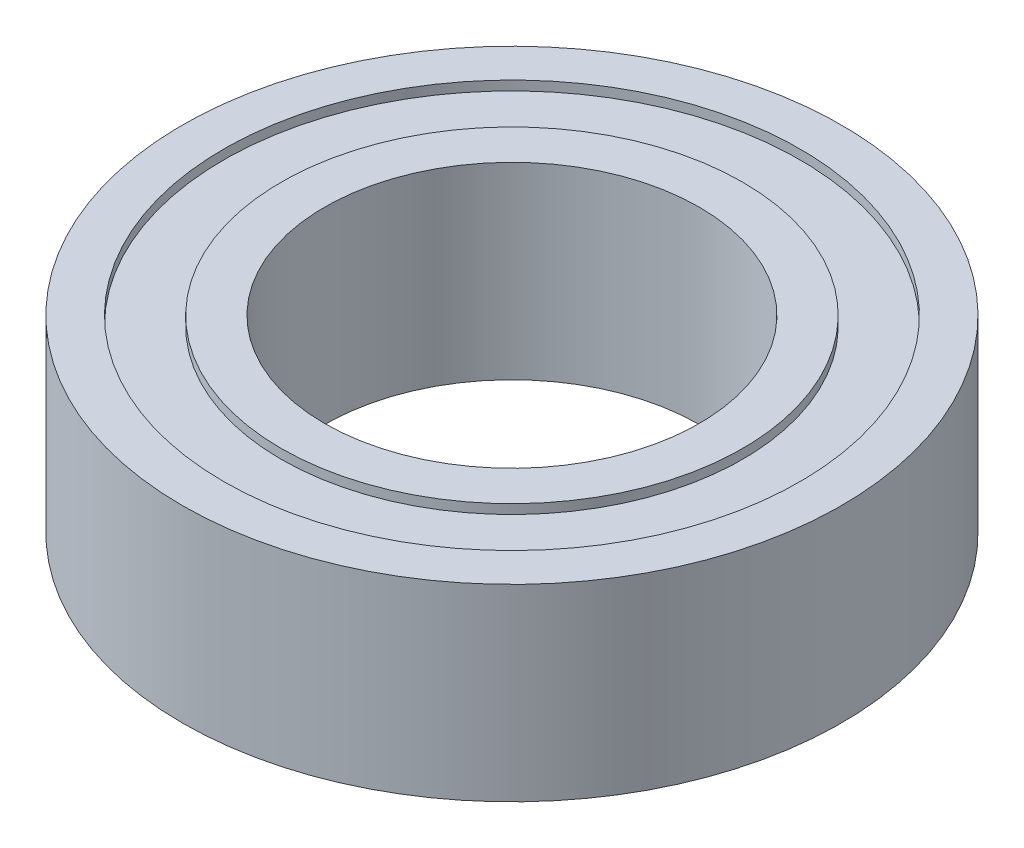
SolidWorks part; units mm, degrees
ref_plane "Front Plane" through (0, 0, 0) normal (0, 0, 1) x (1, 0, 0)
ref_plane "Top Plane" through (0, 0, 0) normal (0, 1, 0) x (1, 0, 0)
ref_plane "Right Plane" through (0, 0, 0) normal (1, 0, 0) x (0, 0, -1)
sketch "Sketch1" plane through (0, 0, 0) normal (0, 1, 0) x (1, 0, 0)
  circle A0 centre (0, 0) radius 7
  dimension "D1" = 14
extrude "Boss-Extrude1" add sketch "Sketch1" along normal mid plane 4
sketch "Sketch2" plane through (0, 0, 0) normal (0, 1, 0) x (1, 0, 0)
  circle A0 centre (0, 0) radius 3.98
  dimension "D1" = 7.96
extrude "Cut-Extrude1" cut sketch "Sketch2" against normal through all both and the other way through all
sketch "Sketch3" plane through (0, 0, 0) normal (0, 1, 0) x (1, 0, 0)
  circle A0 centre (0, 0) radius 4.9
  circle A1 centre (0, 0) radius 6.12
  circle A2 centre (0, 0) radius 7 construction
  dimension "D1" = 1.22
  dimension "D2" = 0.88
extrude "Cut-Extrude2" cut sketch "Sketch3" against normal blind 0.2 from surface starting at face at (0, 2, 3.98)
mirror "Mirror1" about plane through (0, 0, 0) normal (0, 1, 0) of "Cut-Extrude2"
